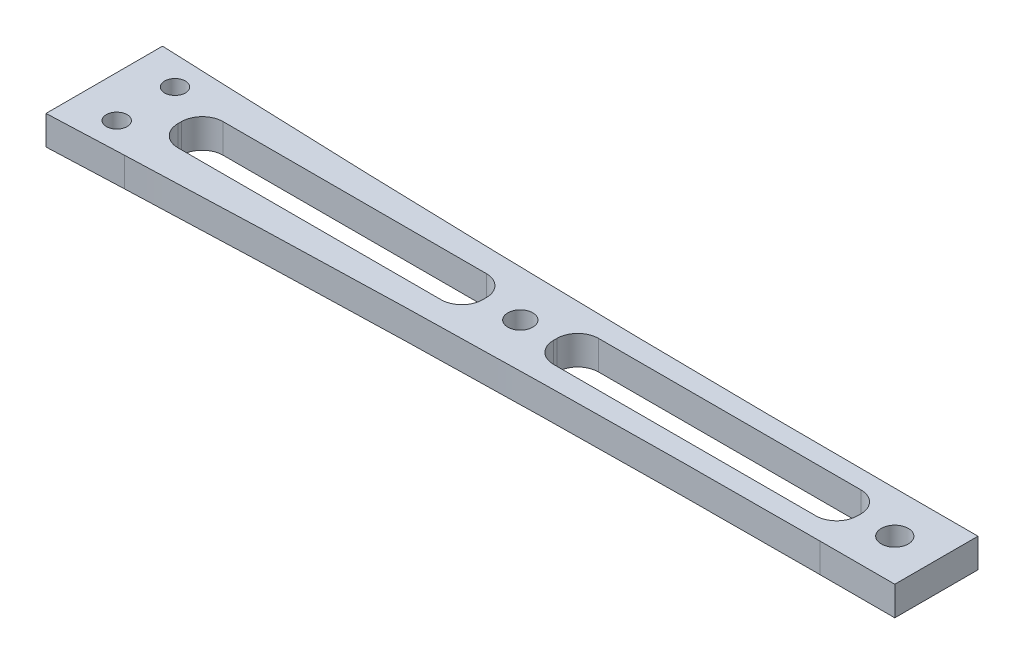
SolidWorks part; units mm, degrees
material "6061 Alloy"
ref_plane "Płaszczyzna przednia" through (0, 0, 0) normal (0, 0, 1) x (1, 0, 0)
ref_plane "Płaszczyzna górna" through (0, 0, 0) normal (0, 1, 0) x (1, 0, 0)
ref_plane "Płaszczyzna prawa" through (0, 0, 0) normal (1, 0, 0) x (0, 0, -1)
sketch "Szkic1" plane through (0, 0, 0) normal (0, 1, 0) x (1, 0, 0)
  line L0 (100, 0) -> (100, 10)
  line L4 (200, 0) -> (200, 20)
  line L5 (0, 10) -> (10, 10)
  line L6 (200, 10) -> (190, 10)
  line L8 (22.9848, 15.5746) -> (86.2594, 15.5746)
  line L9 (17.9848, 10.5746) -> (17.9848, 9.6967)
  line L10 (22.9848, 4.6967) -> (86.2594, 4.6967)
  line L11 (91.2594, 10.5746) -> (91.2594, 9.6967)
  line L12 (113.2251, 15.5746) -> (176.2862, 15.5746)
  line L13 (108.2251, 10.5746) -> (108.2251, 9.7528)
  line L14 (113.2251, 4.7528) -> (176.2862, 4.7528)
  line L15 (181.2862, 10.5746) -> (181.2862, 9.7528)
  line L16 (10, 3) -> (10, 17)
  line L17 (0, -4) -> (100, 0)
  line L18 (200, 0) -> (100, 0)
  line L19 (200, 20) -> (100, 20)
  line L20 (100, 20) -> (0, 24)
  line L21 (0, 24) -> (0, -4)
  circle A0 centre (100, 10) radius 3
  circle A2 centre (190, 10) radius 3.25
  arc A3 (176.2862, 4.7528) -> (181.2862, 9.7528) centre (176.2862, 9.7528) ccw
  arc A4 (181.2862, 10.5746) -> (176.2862, 15.5746) centre (176.2862, 10.5746) ccw
  arc A5 (113.2251, 4.7528) -> (108.2251, 9.7528) centre (113.2251, 9.7528) cw
  arc A6 (113.2251, 15.5746) -> (108.2251, 10.5746) centre (113.2251, 10.5746) ccw
  arc A7 (17.9848, 9.6967) -> (22.9848, 4.6967) centre (22.9848, 9.6967) ccw
  arc A8 (86.2594, 4.6967) -> (91.2594, 9.6967) centre (86.2594, 9.6967) ccw
  arc A9 (91.2594, 10.5746) -> (86.2594, 15.5746) centre (86.2594, 10.5746) ccw
  arc A10 (22.9848, 15.5746) -> (17.9848, 10.5746) centre (22.9848, 10.5746) ccw
  circle A11 centre (10, 17) radius 2.5
  circle A12 centre (10, 3) radius 2.5
  point P39 (0, 10)
  point P42 (10, 10)
  dimension "D1" = 5
extrude "Dodanie-wyciągnięcie1" add sketch "Szkic1" along normal blind 7 contours A0 L4 region at (49.9193, 0, -0.0179)
fillet "Zaokrąglenie1" radius 4100 2 edges at (100, 3.5, -20) (100, 3.5, 0)
